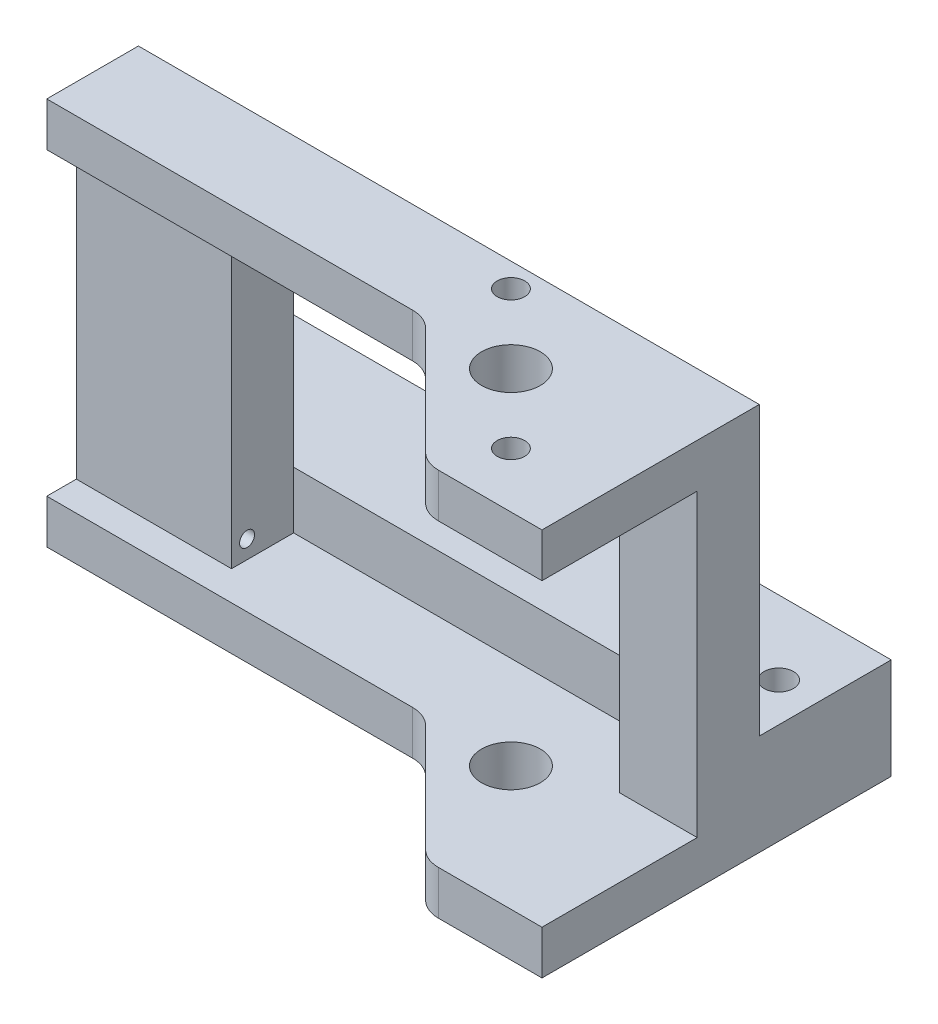
SolidWorks part; units mm, degrees
ref_plane "Front Plane" through (0, 0, 0) normal (0, 0, 1) x (1, 0, 0)
ref_plane "Top Plane" through (0, 0, 0) normal (0, 1, 0) x (1, 0, 0)
ref_plane "Right Plane" through (0, 0, 0) normal (1, 0, 0) x (0, 0, -1)
sketch "Sketch1" plane through (0, 0, 0) normal (0, 0, 1) x (1, 0, 0)
  line L1 (57.15, -31.75) -> (-57.15, -31.75)
  line L2 (57.15, -31.75) -> (57.15, 31.75)
  line L3 (57.15, 31.75) -> (-57.15, 31.75)
  line L4 (-57.15, -31.75) -> (-57.15, 31.75)
  line L5 (57.15, -31.75) -> (-57.15, 31.75) construction
  line L6 (57.15, 31.75) -> (-57.15, -31.75) construction
  point P0 (0, 0)
  dimension "D1" = 63.5
  dimension "D2" = 114.3
extrude "Boss-Extrude1" add sketch "Sketch1" along normal blind 57.15
sketch "Sketch2" plane through (0, 0, 57.15) normal (0, 0, 1) x (1, 0, 0)
  line L0 (-57.15, 31.75) -> (-57.15, -31.75) construction
  line L1 (57.15, -24.55) -> (-57.15, -24.55)
  line L2 (57.15, -24.55) -> (57.15, 24.55)
  line L3 (57.15, 24.55) -> (-57.15, 24.55)
  line L4 (-57.15, -24.55) -> (-57.15, 24.55)
  line L5 (57.15, -24.55) -> (-57.15, 24.55) construction
  line L6 (57.15, 24.55) -> (-57.15, -24.55) construction
  line L7 (57.15, 31.75) -> (-57.15, 31.75) construction
  point P0 (0, 0)
  dimension "D1" = 7.2
extrude "Cut-Extrude2" cut sketch "Sketch2" against normal blind 25.4
sketch "Sketch3" plane through (0, 0, 0) normal (0, 0, -1) x (-1, 0, 0)
  line L0 (-57.15, -31.75) -> (-57.15, 31.75) construction
  line L1 (57.15, 31.75) -> (-57.15, 31.75)
  line L2 (57.15, 31.75) -> (57.15, -15.24)
  line L3 (57.15, -15.24) -> (-57.15, -15.24)
  line L4 (-57.15, 31.75) -> (-57.15, -15.24)
  dimension "D1" = 46.99
extrude "Cut-Extrude3" cut sketch "Sketch3" against normal blind 21.59
sketch "Sketch5" plane through (0, -31.75, 0) normal (0, -1, 0) x (1, 0, 0)
  line L0 (0, 12.06) -> (50.8, 12.06) construction
  line L1 (57.15, 21.59) -> (-57.15, 21.59) construction
  line L2 (57.15, 57.15) -> (57.15, 0) construction
  circle A0 centre (0, 12.06) radius 2.415
  circle A1 centre (50.8, 12.06) radius 2.415
  dimension "D3" = 4.83
  dimension "D4" = 6.35
  dimension "D1" = 9.53
  dimension "D2" = 50.8
extrude "Cut-Extrude4" cut sketch "Sketch5" against normal blind 25.4
sketch "Sketch6" plane through (0, 0, 21.59) normal (0, 0, -1) x (-1, 0, 0)
  line L0 (-53.215, -15.24) -> (2.415, -15.24) construction
  line L1 (-53.215, -15.24) -> (-53.215, -31.75) construction
  line L2 (2.415, -31.75) -> (2.415, -15.24) construction
  line L3 (-57.15, -15.24) -> (57.15, -15.24) construction
  line L5 (-261.62, 3.81) -> (247.65, 3.81) construction
  circle A1 centre (-5.08, -1.524) radius 2.2225
  dimension "D2" = 5.08
  dimension "D3" = 4.445
  dimension "D1" = 5.334
extrude "Cut-Extrude5" cut sketch "Sketch6" against normal blind 5.08
sketch "Sketch7" plane through (0, -31.75, 0) normal (0, -1, 0) x (1, 0, 0)
  line L0 (57.15, 57.15) -> (57.15, 0) construction
  line L2 (-57.15, 31.75) -> (57.15, 31.75) construction
  circle A0 centre (31.75, 36.83) radius 4.8
  dimension "D1" = 9.6
  dimension "D2" = 25.4
  dimension "D3" = 5.08
extrude "Cut-Extrude6" cut sketch "Sketch7" against normal up to surface (63.5 mm away) up to face at (0, 31.75, 39.37)
sketch "Sketch8" plane through (0, 31.75, 0) normal (0, 1, 0) x (1, 0, 0)
  line L0 (20.4363, -25.5163) -> (43.0637, -48.1437) construction
  line L1 (57.15, -31.75) -> (-57.15, -31.75) construction
  circle A0 centre (31.75, -36.83) radius 16 construction
  circle A1 centre (20.4363, -25.5163) radius 2.25
  circle A2 centre (43.0637, -48.1437) radius 2.25
  dimension "D1" = 32
  dimension "D2" = 4.5
  dimension "D3" = 45
sketch "Sketch9" plane through (0, 0, 31.75) normal (0, 0, 1) x (1, 0, 0)
  line L0 (57.15, 31.75) -> (-57.15, 31.75) construction
  line L5 (57.15, 24.55) -> (-57.15, 24.55) construction
  line L6 (-19.05, 24.55) -> (44.45, 24.55)
  line L7 (-19.05, 24.55) -> (-19.05, -24.55)
  line L8 (-19.05, -24.55) -> (44.45, -24.55)
  line L9 (44.45, 24.55) -> (44.45, -24.55)
  line L10 (-57.15, -24.55) -> (57.15, -24.55) construction
  line L11 (-57.15, 24.55) -> (-57.15, -24.55) construction
  line L12 (57.15, -24.55) -> (57.15, 24.55) construction
  line L13 (-57.15, -31.75) -> (-44.45, -31.75)
  line L14 (-57.15, -31.75) -> (-57.15, 31.75)
  line L15 (-57.15, 31.75) -> (-44.45, 31.75)
  line L16 (-44.45, -31.75) -> (-44.45, 31.75)
  line L17 (-57.15, -31.75) -> (-44.45, 31.75) construction
  line L18 (-57.15, 31.75) -> (-44.45, -31.75) construction
  line L19 (-57.15, -31.75) -> (57.15, -31.75) construction
  point P5 (-50.8, 0)
  dimension "D1" = 12.7
  dimension "25in" = 38.1
  dimension "D2" = 12.7
extrude "Cut-Extrude7" cut sketch "Sketch9" against normal through all both and the other way through all
extrude "Cut-Extrude8" cut sketch "Sketch8" against normal up to next
sketch "Sketch10" [suppressed] plane through (0, 0, 29.21) normal (0, 0, 1) x (1, 0, 0)
  line L1 (-30.607, -1.778) -> (-30.607, -6.604) construction
  circle A0 centre (-33.2489, -4.191) radius 2.286
  point P5 (-30.607, -4.191)
  dimension "D1" = 4.572
sketch "Sketch11" [suppressed] plane through (0, 0, 21.59) normal (0, 0, -1) x (-1, 0, 0)
  circle A0 centre (33.2489, -4.191) radius 2.286
  dimension "D1" = 4.572
extrude "Cut-Extrude9" [suppressed] cut sketch "Sketch11" against normal blind 3.81
sketch "Sketch12" plane through (-19.05, 0, 0) normal (1, 0, 0) x (0, 0, -1)
  line L0 (-31.75, -24.55) -> (-31.75, 24.55) construction
  line L1 (-29.21, -21.59) -> (-29.21, 21.59) construction
  line L2 (-21.59, 24.55) -> (-21.59, -15.24) construction
  circle A0 centre (-29.21, -21.59) radius 1.225
  circle A1 centre (-29.21, 21.59) radius 1.225
  point P0 (-31.75, 0)
  point P8 (-29.21, 0)
  dimension "D1" = 2.45
  dimension "D2" = 7.62
  dimension "D3" = 43.18
extrude "Cut-Extrude10" cut sketch "Sketch12" against normal up to surface (25.4 mm away) up to face at (-44.45, -3.048, 33.528)
sketch "Sketch13" plane through (0, 31.75, 0) normal (0, 1, 0) x (1, 0, 0)
  line L0 (-44.45, -36.5854) -> (17.5354, -36.5854)
  line L1 (17.5354, -36.5854) -> (38.1, -57.15)
  line L2 (57.15, -57.15) -> (-44.45, -57.15) construction
  line L3 (43.0637, -48.1437) -> (20.4363, -25.5163) construction
  line L4 (-44.45, -36.5854) -> (-44.45, -57.15)
  line L5 (-44.45, -57.15) -> (38.1, -57.15)
  line L6 (-44.45, -21.59) -> (-44.45, -57.15) construction
extrude "Cut-Extrude12" cut sketch "Sketch13" against normal through all
fillet "Fillet1" radius 5.08 4 edges at (38.1, -28.15, 57.15) (38.1, 28.15, 57.15) (17.5354, 28.15, 36.5854) (17.5354, -28.15, 36.5854)
sketch "Sketch14" plane through (44.45, 0, 0) normal (-1, 0, 0) x (0, 0, 1)
  line L0 (0, -24.55) -> (31.75, -24.55) construction
  line L1 (21.59, -15.24) -> (0, -15.24)
  line L2 (21.59, -15.24) -> (21.59, -24.55)
  line L3 (21.59, -24.55) -> (0, -24.55)
  line L4 (0, -15.24) -> (0, -24.55)
extrude "Boss-Extrude2" add sketch "Sketch14" along normal up to next
